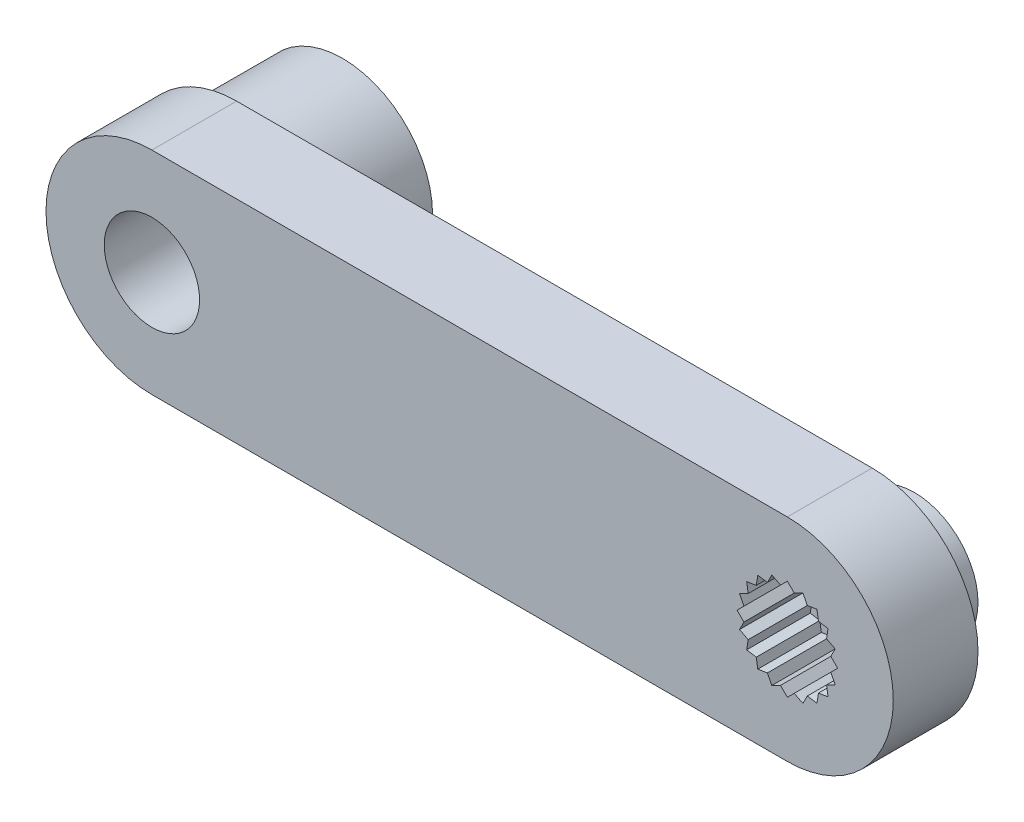
SolidWorks part; units mm, degrees
material "PET"
ref_plane "Front Plane" through (0, 0, 0) normal (0, 0, 1) x (1, 0, 0)
ref_plane "Top Plane" through (0, 0, 0) normal (0, 1, 0) x (1, 0, 0)
ref_plane "Right Plane" through (0, 0, 0) normal (1, 0, 0) x (0, 0, -1)
sketch "Sketch1" plane through (0, 0, 0) normal (0, 0, 1) x (1, 0, 0)
  line L0 (0, 0) -> (30, 0) construction
  line L1 (0, 5) -> (30, 5)
  line L2 (0, -5) -> (30, -5)
  arc A0 (0, 5) -> (0, -5) centre (0, 0) ccw
  arc A1 (30, -5) -> (30, 5) centre (30, 0) ccw
  circle A2 centre (0, 0) radius 2.25
  circle A4 centre (30, 0) radius 1
  point P3 (15, 0)
  dimension "D1" = 5
  dimension "D3" = 4.5
  dimension "D4" = 2
  dimension "D2" = 30
extrude "Boss-Extrude1" add sketch "Sketch1" along normal mid plane 4
sketch "Sketch3" plane through (0, 0, -2) normal (0, 0, -1) x (-1, 0, 0)
  circle A2 centre (-30, 0) radius 3
  circle A4 centre (-30, 0) radius 1 construction
  circle A5 centre (-30, 0) radius 1
  dimension "D1" = 6
extrude "Boss-Extrude2" add sketch "Sketch3" along normal blind 2
sketch "Sketch4" plane through (0, 0, -2) normal (0, 0, -1) x (-1, 0, 0)
  circle A0 centre (0, 0) radius 2.25 construction
  circle A1 centre (0, 0) radius 2.25
  circle A2 centre (0, 0) radius 4.25
  dimension "D1" = 2
extrude "Boss-Extrude3" add sketch "Sketch4" along normal blind 5
sketch "Sketch6" plane through (0, 0, 2) normal (0, 0, 1) x (1, 0, 0)
  line L0 (30, 2.0758) -> (30, 2.375) construction
  line L1 (29.6753, 2.0503) -> (30, 2.375)
  line L2 (30.3247, 2.0503) -> (30, 2.375)
  line L3 (30.3247, 2.0503) -> (30.7339, 2.2588)
  line L4 (30.9424, 1.8496) -> (30.7339, 2.2588)
  line L5 (30.9424, 1.8496) -> (31.396, 1.9214)
  line L6 (31.4678, 1.4678) -> (31.396, 1.9214)
  line L7 (31.4678, 1.4678) -> (31.9214, 1.396)
  line L8 (31.8496, 0.9424) -> (31.9214, 1.396)
  line L9 (31.8496, 0.9424) -> (32.2588, 0.7339)
  line L10 (32.0503, 0.3247) -> (32.2588, 0.7339)
  line L11 (32.0503, 0.3247) -> (32.375, 0)
  line L12 (32.0503, -0.3247) -> (32.375, 0)
  line L13 (32.0503, -0.3247) -> (32.2588, -0.7339)
  line L14 (31.8496, -0.9424) -> (32.2588, -0.7339)
  line L15 (31.8496, -0.9424) -> (31.9214, -1.396)
  line L16 (31.4678, -1.4678) -> (31.9214, -1.396)
  line L17 (31.4678, -1.4678) -> (31.396, -1.9214)
  line L18 (30.9424, -1.8496) -> (31.396, -1.9214)
  line L19 (30.9424, -1.8496) -> (30.7339, -2.2588)
  line L20 (30.3247, -2.0503) -> (30.7339, -2.2588)
  line L21 (30.3247, -2.0503) -> (30, -2.375)
  line L22 (29.6753, -2.0503) -> (30, -2.375)
  line L23 (29.6753, -2.0503) -> (29.2661, -2.2588)
  line L24 (29.0576, -1.8496) -> (29.2661, -2.2588)
  line L25 (29.0576, -1.8496) -> (28.604, -1.9214)
  line L26 (28.5322, -1.4678) -> (28.604, -1.9214)
  line L27 (28.5322, -1.4678) -> (28.0786, -1.396)
  line L28 (28.1504, -0.9424) -> (28.0786, -1.396)
  line L29 (28.1504, -0.9424) -> (27.7412, -0.7339)
  line L30 (27.9497, -0.3247) -> (27.7412, -0.7339)
  line L31 (27.9497, -0.3247) -> (27.625, 0)
  line L32 (27.9497, 0.3247) -> (27.625, 0)
  line L33 (27.9497, 0.3247) -> (27.7412, 0.7339)
  line L34 (28.1504, 0.9424) -> (27.7412, 0.7339)
  line L35 (28.1504, 0.9424) -> (28.0786, 1.396)
  line L36 (28.5322, 1.4678) -> (28.0786, 1.396)
  line L37 (28.5322, 1.4678) -> (28.604, 1.9214)
  line L38 (29.0576, 1.8496) -> (28.604, 1.9214)
  line L39 (29.0576, 1.8496) -> (29.2661, 2.2588)
  line L40 (29.6753, 2.0503) -> (29.2661, 2.2588)
  circle A0 centre (30, 0) radius 2.375 construction
  circle A1 centre (30, 0) radius 2.0758 construction
  circle A3 centre (30, 0) radius 1 construction
  point P9 (0, 0)
  point P10 (30, 0)
  point P67 (30, 0)
  dimension "D1" = 20
  dimension "D2" = 4.75
  dimension "D3" = 45
extrude "Cut-Extrude1" cut sketch "Sketch6" against normal blind 3
